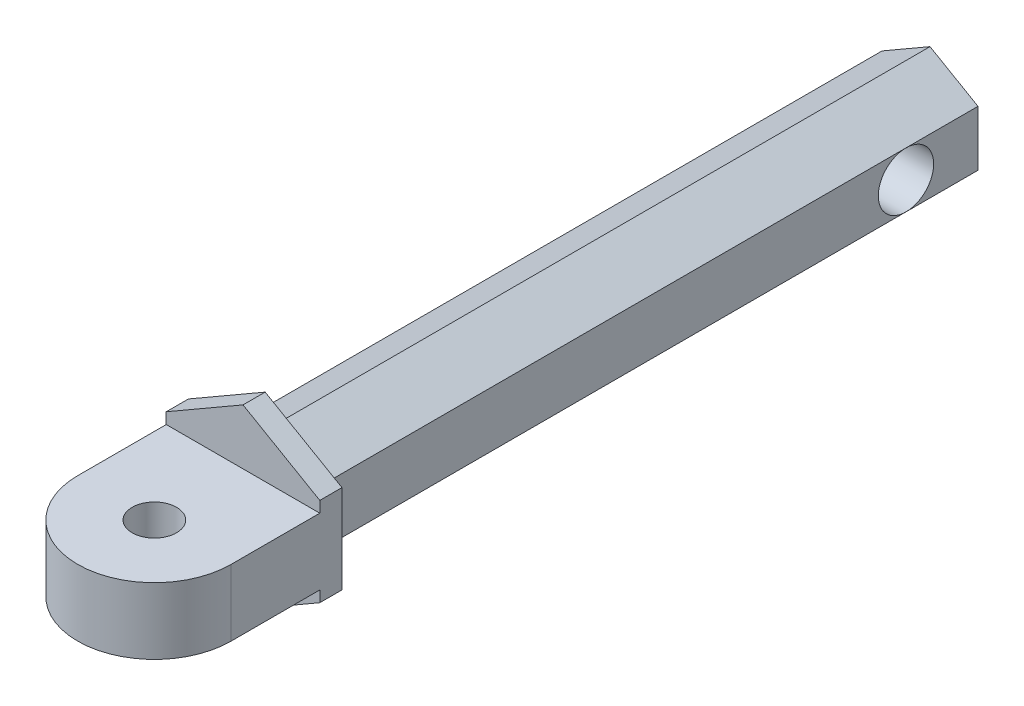
SolidWorks part; units mm, degrees
ref_plane "정면" through (0, 0, 0) normal (0, 0, 1) x (1, 0, 0)
ref_plane "윗면" through (0, 0, 0) normal (0, 1, 0) x (1, 0, 0)
ref_plane "우측면" through (0, 0, 0) normal (1, 0, 0) x (0, 0, -1)
sketch "스케치1" plane through (0, 0, 0) normal (0, 0, 1) x (1, 0, 0)
  line L1 (0, 4) -> (-3.4641, 2)
  line L2 (-3.4641, 2) -> (-3.4641, -2)
  line L3 (-3.4641, -2) -> (0, -4)
  line L4 (0, -4) -> (3.4641, -2)
  line L5 (3.4641, -2) -> (3.4641, 2)
  line L6 (3.4641, 2) -> (0, 4)
  line L7 (0, 3) -> (-2.5981, 1.5)
  line L8 (-2.5981, 1.5) -> (-2.5981, -1.5)
  line L9 (-2.5981, -1.5) -> (0, -3)
  line L10 (0, -3) -> (2.5981, -1.5)
  line L11 (2.5981, -1.5) -> (2.5981, 1.5)
  line L12 (2.5981, 1.5) -> (0, 3)
  circle A0 centre (0, 0) radius 3.4641 construction
  circle A1 centre (0, 0) radius 2.5981 construction
  dimension "D1" = 8
  dimension "D2" = 1
extrude "보스-돌출1" add sketch "스케치1" along normal blind 1 contours L6 L1 L2 L3 L4 L5
sketch "스케치2" plane through (0, 0, 0) normal (0, 1, 0) x (1, 0, 0)
  line L0 (3.4641, -1) -> (3.4641, 0) construction
  line L1 (-3.4641, -1) -> (3.4641, -1)
  line L2 (-3.4641, -1) -> (-3.4641, -5)
  line L4 (3.4641, -1) -> (3.4641, -5)
  arc A0 (-3.4641, -5) -> (3.4641, -5) centre (0, -5) ccw
  circle A1 centre (0, -5) radius 1
  dimension "D2" = 2
  dimension "D1" = 4
extrude "보스-돌출3" add sketch "스케치2" along normal blind 1.5 and the other way blind 1.5
sketch "스케치3" plane through (0, 0, 0) normal (0, 0, -1) x (-1, 0, 0)
  line L1 (0, 2.5) -> (-2.1651, 1.25)
  line L2 (-2.1651, 1.25) -> (-2.1651, -1.25)
  line L3 (-2.1651, -1.25) -> (0, -2.5)
  line L4 (0, -2.5) -> (2.1651, -1.25)
  line L5 (2.1651, -1.25) -> (2.1651, 1.25)
  line L6 (2.1651, 1.25) -> (0, 2.5)
  circle A0 centre (0, 0) radius 2.1651 construction
  dimension "D1" = 1.5
extrude "보스-돌출4" add sketch "스케치3" along normal blind 30
sketch "스케치4" plane through (-2.1651, 0, 0) normal (-1, 0, 0) x (0, 0, 1)
  line L0 (-30, -1.25) -> (-30, 1.25) construction
  circle A0 centre (-26.75, 0) radius 1.25
  dimension "D1" = 2.5
  dimension "D2" = 3.25
extrude "컷-돌출1" cut sketch "스케치4" against normal up to surface (4.3301 mm away) contours A0 up to face at (2.1651, 0, -15)
